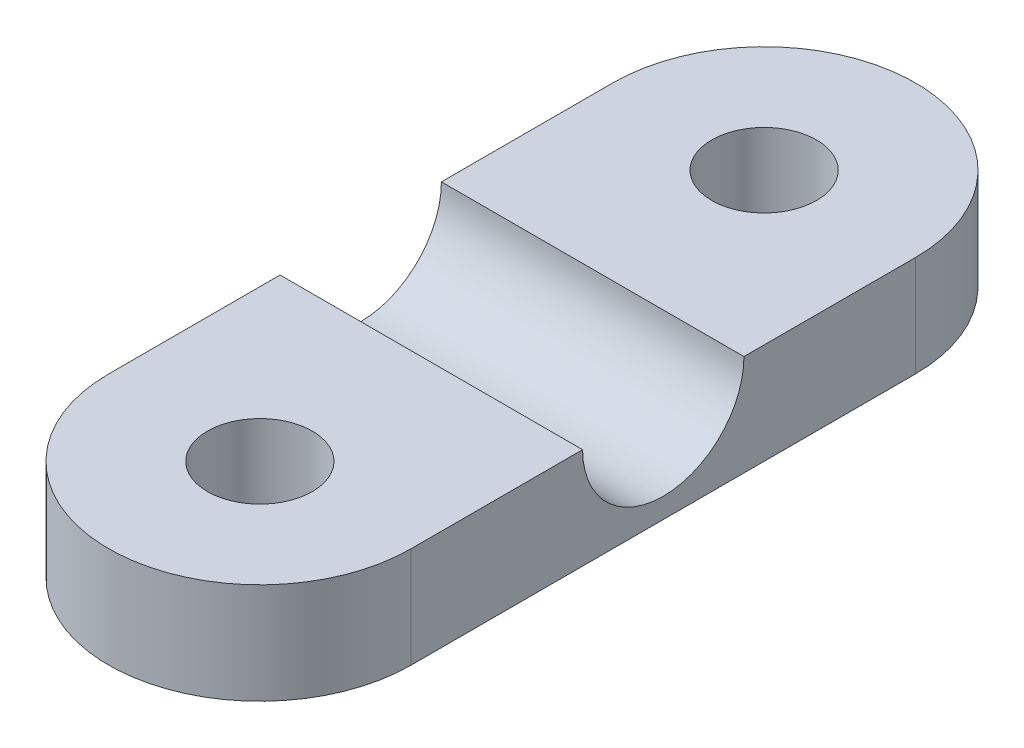
SolidWorks part; units mm, degrees
ref_plane "Front Plane" through (0, 0, 0) normal (0, 0, 1) x (1, 0, 0)
ref_plane "Top Plane" through (0, 0, 0) normal (0, 1, 0) x (1, 0, 0)
ref_plane "Right Plane" through (0, 0, 0) normal (1, 0, 0) x (0, 0, -1)
sketch "Sketch1" plane through (0, 0, 0) normal (0, 1, 0) x (1, 0, 0)
  line L0 (0, 20) -> (0, -20) construction
  line L1 (-7.5, 20) -> (7.5, 20)
  line L2 (-7.5, 20) -> (-7.5, -20)
  line L3 (-7.5, -20) -> (7.5, -20)
  line L4 (7.5, 20) -> (7.5, -20)
  line L5 (-7.5, 20) -> (7.5, -20) construction
  line L6 (-7.5, -20) -> (7.5, 20) construction
  line L7 (-7.5, 0) -> (7.5, 0) construction
  circle A0 centre (0, 12.5) radius 7.5
  circle A1 centre (0, 12.5) radius 2.6
  circle A2 centre (0, -12.5) radius 2.6
  circle A3 centre (0, -12.5) radius 7.5
  point P0 (0, 0)
  dimension "D3" = 5.2
  dimension "D1" = 15
  dimension "D2" = 40
extrude "Boss-Extrude1" add sketch "Sketch1" along normal blind 5 contours A0 A1 | L2 A3 L4 A0 | A3 A2 region at (5.1533, 0, -17.6533) region at (0, 0, 0) region at (0, 0, 5.2121)
sketch "Sketch2" plane through (7.5, 0, 0) normal (1, 0, 0) x (0, 0, -1)
  line L0 (12.5, 5) -> (-12.5, 5) construction
  circle A0 centre (0, 5) radius 4
  dimension "D1" = 8
extrude "Cut-Extrude1" cut sketch "Sketch2" against normal up to next
